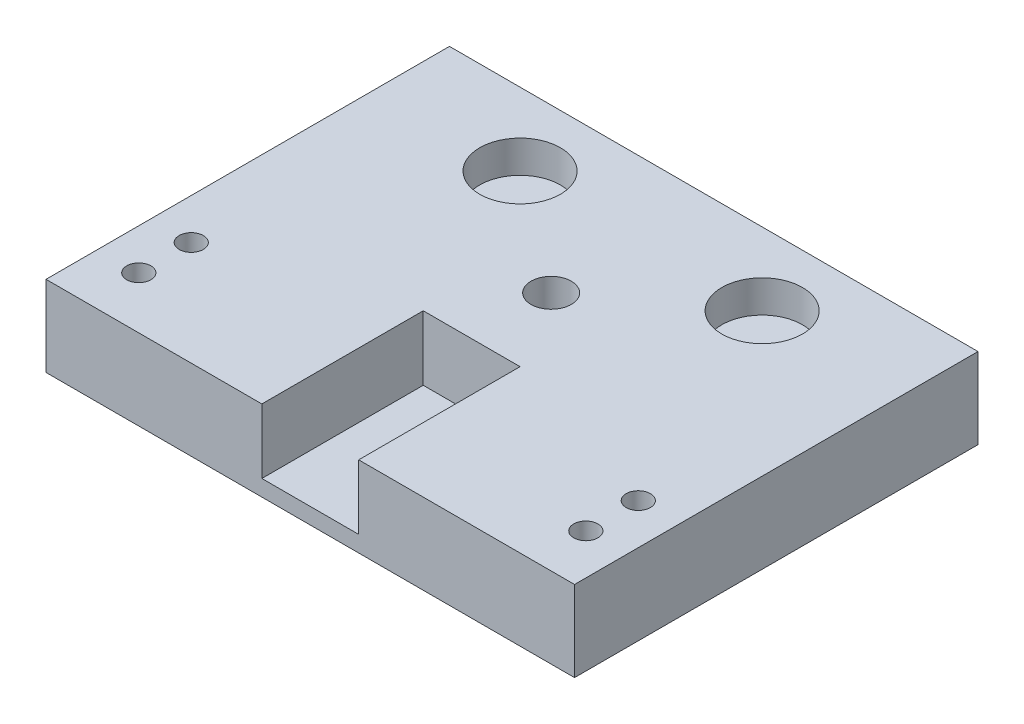
SolidWorks part; units mm, degrees
ref_plane "Płaszczyzna przednia" through (0, 0, 0) normal (0, 0, 1) x (1, 0, 0)
ref_plane "Płaszczyzna górna" through (0, 0, 0) normal (0, 1, 0) x (1, 0, 0)
ref_plane "Płaszczyzna prawa" through (0, 0, 0) normal (1, 0, 0) x (0, 0, -1)
sketch "Sketch1" plane through (0, 0, 0) normal (0, 0, 1) x (1, 0, 0)
  line L0 (26.75, 10) -> (26.75, 2)
  line L1 (0, 0) -> (65.5, 0)
  line L2 (0, 0) -> (0, 10)
  line L3 (0, 10) -> (26.75, 10)
  line L4 (65.5, 0) -> (65.5, 10)
  line L5 (26.75, 2) -> (38.75, 2)
  line L6 (38.75, 2) -> (38.75, 10)
  line L7 (38.75, 10) -> (65.5, 10)
  dimension "D1" = 65.5
  dimension "D2" = 10
  dimension "D3" = 26.75
  dimension "D4" = 26.75
  dimension "D5" = 8
extrude "Boss-Extrude1" add sketch "Sketch1" along normal blind 20
sketch "Sketch14" [suppressed] plane through (0, 0, 0) normal (0, 0, 1) x (1, 0, 0)
  line L1 (65.5, 0) -> (0, 0)
  line L2 (65.5, 0) -> (65.5, 14)
  line L3 (65.5, 14) -> (0, 14)
  line L4 (0, 0) -> (0, 14)
  line L5 (65.5, 0) -> (0, 14) construction
  line L6 (65.5, 14) -> (0, 0) construction
  point P4 (32.75, 7)
extrude "Boss-Extrude2" [suppressed] add sketch "Sketch14" along normal blind 20
hole_wizard "Ø3.2 (3.2) Diameter Hole1" positions "Sketch8" profile "Sketch9" hole size "Ø3.2" standard "ANSI Metric"
sketch "Sketch8" plane through (0, 0, 0) normal (0, 1, 0) x (1, 0, 0)
  point P0 (32.75, -10)
sketch "Sketch9" plane through (32.75, 0, 10) normal (1, 0, 0) x (0, 0, -1)
  line L0 (0, 0) -> (0, 12.9614)
  line L1 (0, 12.9614) -> (1.6, 12)
  line L2 (1.6, 12) -> (1.6, 0)
  line L5 (1.6, 0) -> (0, 0)
  line L10 (0, 12.9614) -> (-1.6, 12) construction
  line L11 (0, -6.35) -> (0, 107.95) construction
  dimension "Hole Dia." = 3.2
  dimension "Hole Depth" = 12
  dimension "Drill Angle" = 118
sketch "Sketch13" plane through (0, 0, 0) normal (0, -1, 0) x (1, 0, 0)
  circle A0 centre (5.05, 7.05) radius 1.5
  circle A1 centre (5.05, 13.55) radius 1.5
  circle A2 centre (60.45, 7.05) radius 1.5
  circle A3 centre (60.45, 13.55) radius 1.5
extrude "Cut-Extrude2" cut sketch "Sketch13" against normal blind 54
sketch "Sketch15" plane through (0, 0, 0) normal (0, 0, -1) x (-1, 0, 0)
  line L1 (-65.5, 0) -> (0, 0)
  line L2 (-65.5, 0) -> (-65.5, 10)
  line L3 (-65.5, 10) -> (0, 10)
  line L4 (0, 0) -> (0, 10)
  line L5 (-65.5, 0) -> (0, 10) construction
  line L6 (-65.5, 10) -> (0, 0) construction
  point P4 (-32.75, 5)
extrude "Boss-Extrude3" add sketch "Sketch15" along normal blind 30
sketch "Sketch16" plane through (0, 10, 0) normal (0, 1, 0) x (1, 0, 0)
  line L0 (0, -20) -> (0, 30) construction
  line L1 (26.75, -20) -> (0, -20) construction
  circle A0 centre (32.75, 9.85) radius 2.5
  dimension "D1" = 32.75
  dimension "D2" = 29.85
  dimension "D3" = 5
extrude "Cut-Extrude4" cut sketch "Sketch16" against normal blind 10
sketch "Sketch18" plane through (0, 0, 0) normal (0, -1, 0) x (1, 0, 0)
  line L0 (0, 20) -> (65.5, 20) construction
  line L1 (0, 20) -> (0, -30) construction
  line L2 (65.5, 20) -> (65.5, -30) construction
  circle A0 centre (52.75, -9.85) radius 5
  circle A1 centre (12.75, -9.85) radius 5
  dimension "D1" = 10
  dimension "D2" = 10
  dimension "D3" = 29.85
  dimension "D4" = 29.85
  dimension "D5" = 12.75
  dimension "D6" = 12.75
extrude "Cut-Extrude5" cut sketch "Sketch18" against normal blind 4
sketch "Sketch19" plane through (0, 10, 0) normal (0, 1, 0) x (1, 0, 0)
  line L0 (26.75, -20) -> (0, -20) construction
  line L1 (65.5, -20) -> (38.75, -20) construction
  line L2 (65.5, -20) -> (65.5, 30) construction
  line L3 (0, -20) -> (0, 30) construction
  circle A0 centre (47.75, 21) radius 5
  circle A1 centre (17.75, 21) radius 5
  dimension "D2" = 41
  dimension "D3" = 10
  dimension "D4" = 10
  dimension "D5" = 17.75
  dimension "D6" = 17.75
  dimension "D1" = 41
extrude "Cut-Extrude6" cut sketch "Sketch19" against normal blind 4
